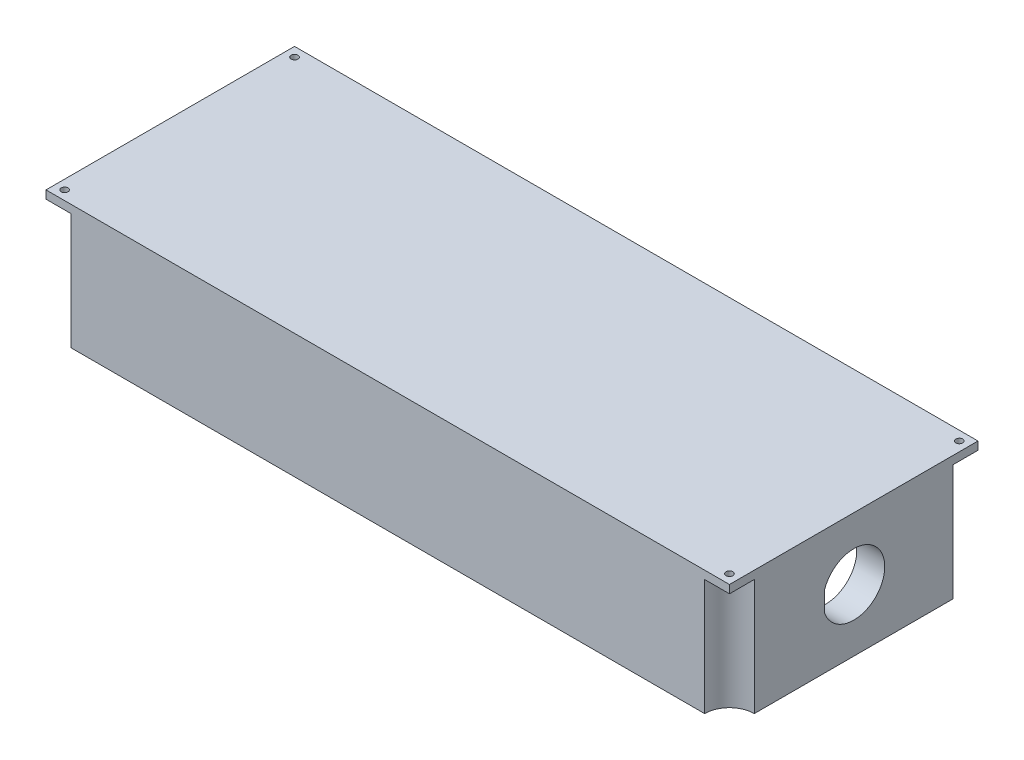
SolidWorks part; units mm, degrees
ref_plane "Front Plane" through (0, 0, 0) normal (0, 0, 1) x (1, 0, 0)
ref_plane "Top Plane" through (0, 0, 0) normal (0, 1, 0) x (1, 0, 0)
ref_plane "Right Plane" through (0, 0, 0) normal (1, 0, 0) x (0, 0, -1)
sketch "Sketch1" plane through (0, 0, 0) normal (0, 1, 0) x (1, 0, 0)
  line L0 (114.3, 50.8) -> (165.1, 50.8)
  line L1 (-114.3, 50.8) -> (114.3, 50.8)
  line L2 (-114.3, 50.8) -> (-114.3, -50.8)
  line L3 (-114.3, -50.8) -> (114.3, -50.8)
  line L5 (-114.3, 50.8) -> (114.3, -50.8) construction
  line L6 (-114.3, -50.8) -> (114.3, 50.8) construction
  line L7 (165.1, 50.8) -> (165.1, -50.8)
  line L8 (165.1, -50.8) -> (114.3, -50.8)
  point P0 (0, 0)
  dimension "D1" = 101.6
  dimension "D2" = 228.6
  dimension "D3" = 50.8
extrude "Boss-Extrude1" add sketch "Sketch1" against normal blind 50.8
sketch "Sketch2" plane through (0, 0, 0) normal (0, 1, 0) x (1, 0, 0)
  line L1 (-102.87, 39.37) -> (102.87, 39.37)
  line L2 (-102.87, 39.37) -> (-102.87, -39.37)
  line L3 (-102.87, -39.37) -> (102.87, -39.37)
  line L4 (102.87, 39.37) -> (102.87, -39.37)
  line L5 (-102.87, 39.37) -> (102.87, -39.37) construction
  line L6 (-102.87, -39.37) -> (102.87, 39.37) construction
  point P0 (0, 0)
  dimension "D1" = 205.74
  dimension "D2" = 78.74
extrude "Cut-Extrude1" cut sketch "Sketch2" against normal blind 101.6
sketch "Sketch14" plane through (0, 0, 39.37) normal (0, 0, -1) x (-1, 0, 0)
  line L1 (-102.87, 0) -> (102.87, 0)
  line L2 (-102.87, 0) -> (-102.87, -17.78)
  line L3 (-102.87, -17.78) -> (102.87, -17.78)
  line L4 (102.87, 0) -> (102.87, -17.78)
  point P5 (-102.87, -8.89)
  dimension "D1" = 17.78
  dimension "D2" = 205.74
extrude "mountingEdge" add sketch "Sketch14" along normal blind 10.16
mirror "Mirror1" about plane through (0, 0, 0) normal (0, 0, 1) of "mountingEdge"
sketch "Sketch16" plane through (-102.87, 0, 0) normal (1, 0, 0) x (0, 0, -1)
  line L0 (29.21, -17.78) -> (29.21, 0) construction
  line L1 (-29.21, 0) -> (29.21, 0)
  line L2 (-29.21, 0) -> (-29.21, -3.81)
  line L3 (-29.21, -3.81) -> (29.21, -3.81)
  line L4 (29.21, 0) -> (29.21, -3.81)
  dimension "D1" = 3.81
extrude "bottom" add sketch "Sketch16" along normal up to next
sketch "Sketch17" plane through (0, -3.81, 0) normal (0, -1, 0) x (1, 0, 0)
  line L0 (0, 0) -> (-21.7762, 0) construction
  line L6 (-114.3, -50.8) -> (-114.3, 50.8) construction
  line L7 (-35.052, 17.78) -> (-22.352, 17.78)
  line L12 (-35.052, 17.78) -> (-35.052, 5.08)
  line L13 (-35.052, 5.08) -> (-22.352, 5.08)
  line L14 (-22.352, 17.78) -> (-22.352, 5.08)
  line L19 (-101.6, 38.1) -> (101.6, -38.1) construction
  line L20 (-101.6, -38.1) -> (101.6, 38.1) construction
  line L21 (-19.558, 19.558) -> (-4.572, 19.558)
  line L22 (-19.558, 19.558) -> (-19.558, 4.572)
  line L23 (-19.558, 4.572) -> (-4.572, 4.572)
  line L24 (-4.572, 19.558) -> (-4.572, 4.572)
  line L29 (-114.3, 50.8) -> (165.1, 50.8) construction
  line L30 (16.764, -3.928) -> (26.764, -3.928)
  line L31 (16.764, -3.928) -> (16.764, -15.928)
  line L32 (16.764, -15.928) -> (26.764, -15.928)
  line L33 (26.764, -3.928) -> (26.764, -15.928)
  line L34 (16.764, -3.928) -> (26.764, -15.928) construction
  line L35 (16.764, -15.928) -> (26.764, -3.928) construction
  point P11 (21.764, -9.928)
  dimension "D2" = 79.248
  dimension "D3" = 14.986
  dimension "D4" = 33.02
  dimension "D5" = 12.7
  dimension "D6" = 14.986
  dimension "D7" = 76.2
  dimension "D8" = 203.2
  dimension "D9" = 2.794
  dimension "D10" = 31.242
  dimension "D11" = 12.7
  dimension "D12" = 12
  dimension "D13" = 10
  dimension "D14" = 21.336
  dimension "D15" = 8.5
extrude "rpitowers" add sketch "Sketch17" along normal blind 10.16
sketch "Sketch18" plane through (-114.3, 0, 0) normal (-1, 0, 0) x (0, 0, 1)
  line L0 (-50.8, -50.8) -> (-50.8, 0) construction
  line L1 (-50.8, -33.782) -> (50.8, -33.782)
  line L2 (-50.8, -33.782) -> (-50.8, -50.8)
  line L3 (-50.8, -50.8) -> (50.8, -50.8)
  line L4 (50.8, -33.782) -> (50.8, -50.8)
  line L5 (50.8, -50.8) -> (50.8, 0) construction
  line L6 (-50.8, -50.8) -> (50.8, -50.8) construction
  line L7 (-50.8, 0) -> (50.8, 0) construction
  dimension "D1" = 33.782
extrude "Cut-Extrude6" cut sketch "Sketch18" against normal through all rebuild error yes
ref_plane "Plane6" through (-102.87, -17.78, 29.21) normal (-1, 0, 0) x (0, 0, 1)
sketch "Sketch21" plane through (0, -3.81, 0) normal (0, -1, 0) x (1, 0, 0)
  line L0 (102.87, -29.21) -> (-102.87, -29.21) construction
  line L2 (-102.87, 29.21) -> (-92.71, 29.21)
  line L4 (-102.87, 29.21) -> (-102.87, -29.21)
  line L5 (-102.87, -29.21) -> (-92.71, -29.21)
  line L6 (-92.71, 29.21) -> (-92.71, -29.21)
  dimension "D1" = 10.16
extrude "Boss-Extrude11" add sketch "Sketch21" along normal blind 13.97
sketch "Sketch22" plane through (0, -3.81, 0) normal (0, -1, 0) x (1, 0, 0)
  line L0 (102.87, -29.21) -> (-92.71, -29.21) construction
  line L1 (102.87, 29.21) -> (92.71, 29.21)
  line L2 (102.87, 29.21) -> (102.87, -29.21)
  line L3 (102.87, -29.21) -> (92.71, -29.21)
  line L4 (92.71, 29.21) -> (92.71, -29.21)
  dimension "D1" = 10.16
extrude "Boss-Extrude12" add sketch "Sketch22" along normal blind 13.97
ref_plane "Plane7" through (102.87, -33.782, 39.37) normal (0, 0, 1) x (1, 0, 0)
sketch "Sketch23" plane through (0, -33.782, 0) normal (0, -1, 0) x (-1, 0, 0)
  circle A0 centre (114.3, 50.8) radius 10.16
extrude "MountHole1" cut sketch "Sketch23" against normal blind 30.48 and the other way through all
sketch "Sketch25" plane through (0, -3.302, 0) normal (0, -1, 0) x (1, 0, 0)
  line L0 (-104.14, -50.8) -> (-114.3, -50.8) construction
  line L1 (-114.3, -50.8) -> (-114.3, -40.64) construction
  circle A0 centre (-110.49, -46.99) radius 1.4
  dimension "D1" = 2.8
  dimension "D2" = 3.81
  dimension "D3" = 3.81
extrude "Cut-Extrude7" cut sketch "Sketch25" against normal through all
mirror "Mirror3" about plane through (0, 0, 0) normal (0, 0, 1) of "Cut-Extrude7", "MountHole1"
sketch "Sketch26" plane through (0, 0, 0) normal (0, 0, 1) x (1, 0, 0)
  line L0 (26.764, -13.97) -> (26.764, -3.81) construction
  line L1 (16.764, -13.97) -> (26.764, -13.97)
  line L2 (16.764, -13.97) -> (16.764, -11.938)
  line L3 (16.764, -11.938) -> (26.764, -11.938)
  line L4 (26.764, -13.97) -> (26.764, -11.938)
  dimension "D1" = 2.032
extrude "Cut-Extrude8" cut sketch "Sketch26" against normal blind 25.24
sketch "Sketch28" plane through (0, -33.782, 0) normal (0, -1, 0) x (1, 0, 0)
  line L0 (102.87, 39.37) -> (153.67, 39.37)
  line L3 (153.67, 39.37) -> (153.67, -39.37)
  line L4 (153.67, -39.37) -> (102.87, -39.37)
  line L5 (102.87, -39.37) -> (102.87, 39.37)
  dimension "D1" = 50.8
extrude "Cut-Extrude9" cut sketch "Sketch28" against normal blind 30.48 and the other way through all
sketch "Sketch29" plane through (165.1, 0, 0) normal (1, 0, 0) x (0, 0, -1)
  line L0 (-11.869, -21.109) -> (-11.869, -29.691)
  line L1 (-50.8, -50.8) -> (50.8, -50.8) construction
  arc A0 (-11.869, -29.691) -> (-11.869, -21.109) centre (0.031, -25.4) ccw
  dimension "D1" = 25.3
  dimension "D2" = 11.9
  dimension "D3" = 25.4
extrude "Cut-Extrude10" cut sketch "Sketch29" against normal blind 30.48 and the other way through all
ref_plane "Plane8" through (25.4, 0, 0) normal (1, 0, 0) x (0, 0, -1)
mirror "Mirror4" about plane through (25.4, 0, 0) normal (1, 0, 0) of "Mirror3"
sketch "Sketch33" plane through (0, -33.782, 0) normal (0, -1, 0) x (1, 0, 0)
  line L0 (154.94, -50.8) -> (-104.14, -50.8) construction
  line L1 (165.1, 40.64) -> (165.1, -40.64) construction
  line L2 (-114.3, 40.64) -> (-114.3, -40.64) construction
  circle A0 centre (-88.9, -45.72) radius 1.4224
  circle A1 centre (25.4, -45.72) radius 1.4224
  circle A2 centre (139.7, -45.72) radius 1.4224
  dimension "D1" = 2.8448
  dimension "D2" = 2.8448
  dimension "D3" = 2.8448
  dimension "D4" = 5.08
  dimension "D5" = 5.08
  dimension "D6" = 5.08
  dimension "D7" = 25.4
  dimension "D8" = 25.4
  dimension "D9" = 139.7
extrude "Cut-Extrude14" cut sketch "Sketch33" against normal blind 2.54 and the other way blind 17.78
mirror "Mirror5" about plane through (0, 0, 0) normal (0, 0, 1) of "Cut-Extrude14"
sketch "Sketch35" plane through (102.87, 0, 0) normal (1, 0, 0) x (0, 0, -1)
  line L0 (39.37, -17.78) -> (-39.37, -17.78) construction
  circle A0 centre (1.4935, -14.732) radius 5.715
  dimension "D1" = 11.43
  dimension "D2" = 3.048
extrude "Cut-Extrude16" cut sketch "Sketch35" against normal blind 12.7
sketch "Sketch36" plane through (-114.3, 0, 0) normal (-1, 0, 0) x (0, 0, 1)
  line L0 (-40.64, -50.8) -> (40.64, -50.8) construction
  line L1 (40.64, -3.302) -> (40.64, -50.8) construction
  line L2 (-40.64, -3.302) -> (-40.64, -50.8) construction
  circle A0 centre (15.24, -38.1) radius 6.731
  circle A1 centre (-15.24, -38.1) radius 6.731
  dimension "D1" = 13.462
  dimension "D2" = 13.462
  dimension "D3" = 12.7
  dimension "D4" = 12.7
  dimension "D5" = 25.4
  dimension "D6" = 25.4
extrude "Cut-Extrude17" cut sketch "Sketch36" against normal blind 12.7
sketch "Sketch37" plane through (0, 0, -50.8) normal (0, 0, -1) x (-1, 0, 0)
  line L0 (-154.94, -50.8) -> (104.14, -50.8) construction
  line L1 (-154.94, -50.8) -> (-154.94, -3.302) construction
  circle A0 centre (-135.89, -25.4) radius 5.08
  dimension "D1" = 10.16
  dimension "D2" = 25.4
  dimension "D3" = 19.05
extrude "Cut-Extrude18" cut sketch "Sketch37" against normal blind 12.7
sketch "Sketch38" plane through (0, -50.8, 0) normal (0, -1, 0) x (1, 0, 0)
  line L0 (-114.3, -40.64) -> (-114.3, 40.64) construction
  line L1 (-104.14, 50.8) -> (154.94, 50.8) construction
  circle A0 centre (-109.22, 0) radius 1.524
  dimension "D1" = 3.048
  dimension "D2" = 5.08
  dimension "D3" = 50.8
extrude "Cut-Extrude19" cut sketch "Sketch38" against normal blind 5.08
mirror "Mirror6" about plane through (25.4, 0, 0) normal (1, 0, 0) of "Cut-Extrude19"
